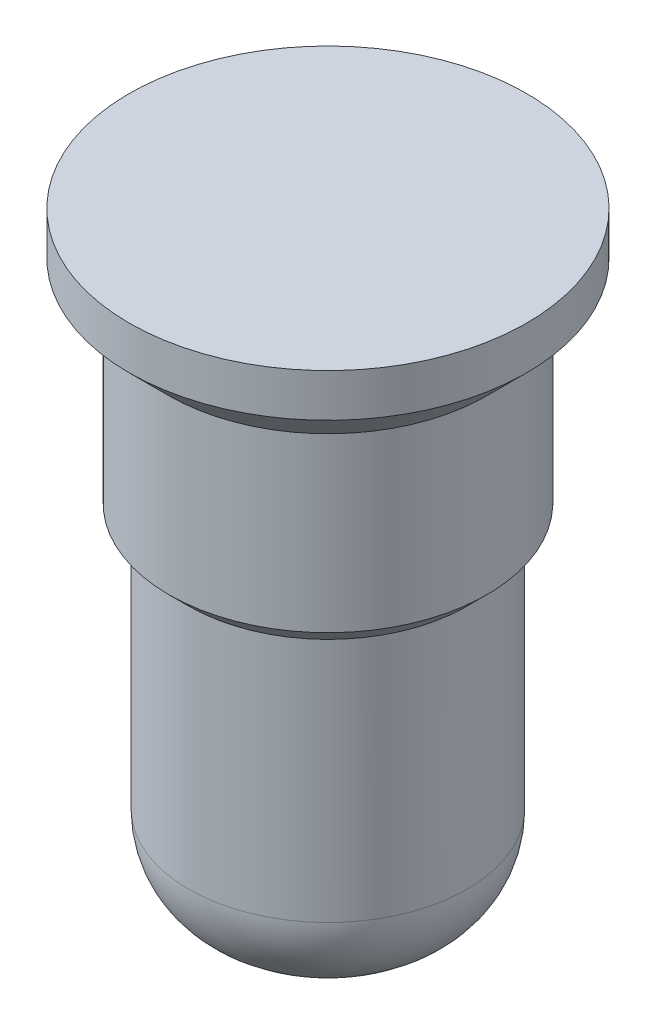
SolidWorks part; units mm, degrees
ref_plane "Front Plane" through (0, 0, 0) normal (0, 0, 1) x (1, 0, 0)
ref_plane "Top Plane" through (0, 0, 0) normal (0, 1, 0) x (1, 0, 0)
ref_plane "Right Plane" through (0, 0, 0) normal (1, 0, 0) x (0, 0, -1)
sketch "Sketch1" plane through (0, 0, 0) normal (0, 1, 0) x (1, 0, 0)
  circle A0 centre (0, 0) radius 1.905
  dimension "D1" = 3.81
extrude "Boss-Extrude1" add sketch "Sketch1" along normal blind 0.7937
sketch "Sketch2" plane through (0, 0, 0) normal (0, -1, 0) x (1, 0, 0)
  circle A0 centre (0, 0) radius 1.524
  dimension "D1" = 3.048
extrude "Boss-Extrude2" add sketch "Sketch2" along normal blind 2.54
chamfer "Chamfer1" distance 0.381 angle 45 1 edges at (0, 0, 1.905)
sketch "Sketch4" plane through (0, -2.54, 0) normal (0, -1, 0) x (1, 0, 0)
  circle A0 centre (0, 0) radius 1.3335
  dimension "D1" = 2.667
extrude "Boss-Extrude3" add sketch "Sketch4" along normal blind 2.54
fillet "Fillet3" radius 0.889 1 edges at (0, -5.08, -1.3335)
chamfer "Chamfer2" distance 0.889 angle 45 1 edges at (0, -2.54, -1.524)
